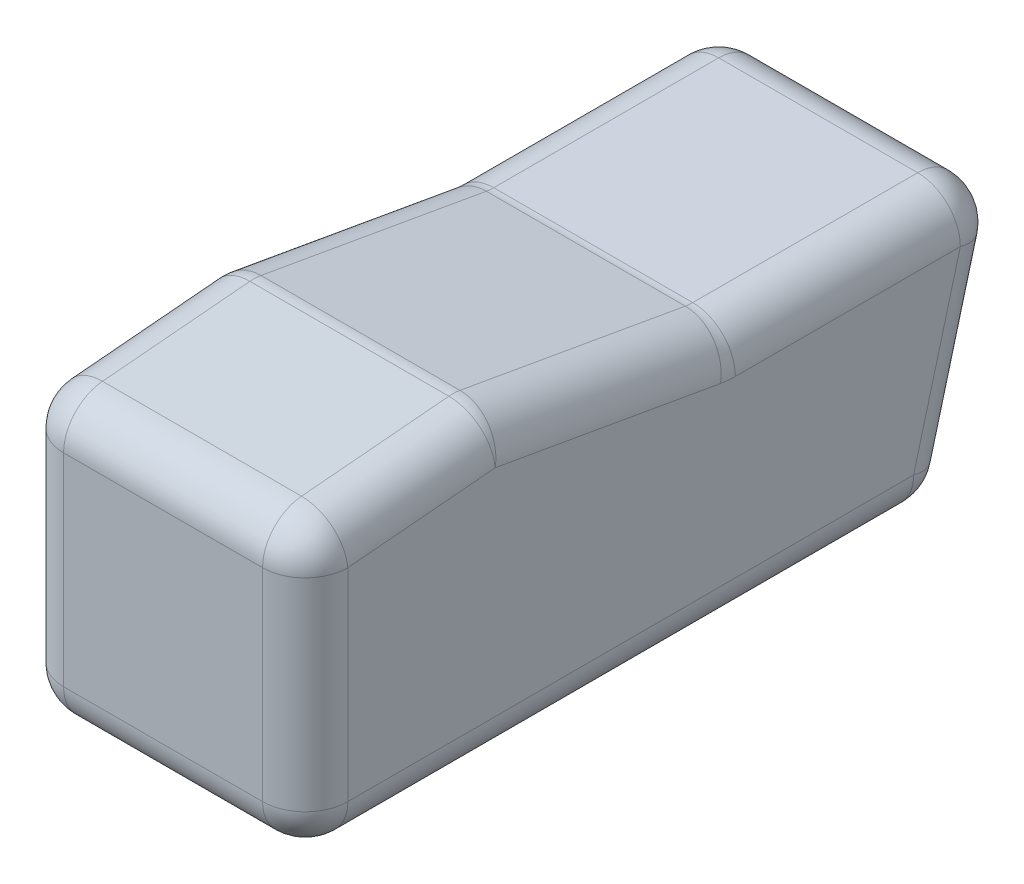
SolidWorks part; units mm, degrees
ref_plane "Ebene vorne" through (0, 0, 0) normal (0, 0, 1) x (1, 0, 0)
ref_plane "Ebene oben" through (0, 0, 0) normal (0, 1, 0) x (1, 0, 0)
ref_plane "Ebene rechts" through (0, 0, 0) normal (1, 0, 0) x (0, 0, -1)
sketch "Skizze2" plane through (0, 0, 0) normal (1, 0, 0) x (0, 0, -1)
  line L0 (500, -1000) -> (500, 1000)
  line L1 (-500, -500) -> (500, -500) construction
  line L2 (-500, -500) -> (-500, 500) construction
  line L3 (-500, 500) -> (500, 500) construction
  line L4 (500, -500) -> (500, 500) construction
  line L5 (-500, -500) -> (500, 500) construction
  line L6 (-500, 500) -> (500, -500) construction
  line L7 (500, 1000) -> (1850, 1118.1097)
  line L8 (1850, 1118.1097) -> (3500, 827.1702)
  line L9 (3500, 827.1702) -> (5500, 827.1702)
  line L10 (5500, 827.1702) -> (5010.4112, -1000)
  line L11 (5010.4112, -1000) -> (500, -1000)
  point P0 (0, 0)
  dimension "D1" = 1000
  dimension "D2" = 1000
  dimension "D3" = 5000
  dimension "D4" = 75
  dimension "D5" = 1350
  dimension "D6" = 1650
  dimension "D7" = 95
  dimension "D8" = 165
  dimension "D9" = 500
  dimension "D10" = 500
extrude "Aufsatz-Linear austragen1" add sketch "Skizze2" along normal blind 1000 and the other way blind 1000 contours L8 L9 L10 L11 L0 L7
fillet "Verrundung1" radius 300 18 edges at (-1000, 827.1702, -4500) (0, 827.1702, -5500) (1000, 827.1702, -4500) (-1000, 972.6399, -2675) (0, 827.1702, -3500) (1000, 972.6399, -2675) (-1000, 1059.0548, -1175) (0, 1118.1097, -1850) (1000, 1059.0548, -1175) (0, 1000, -500) (0, -1000, -500) (-1000, 0, -500) (-1000, -1000, -2755.2056) (-1000, -86.4149, -5255.2056) (0, -1000, -5010.4112) (1000, -86.4149, -5255.2056) (1000, -1000, -2755.2056) (1000, 0, -500)
equation "\"hubDiameter\"=1"
